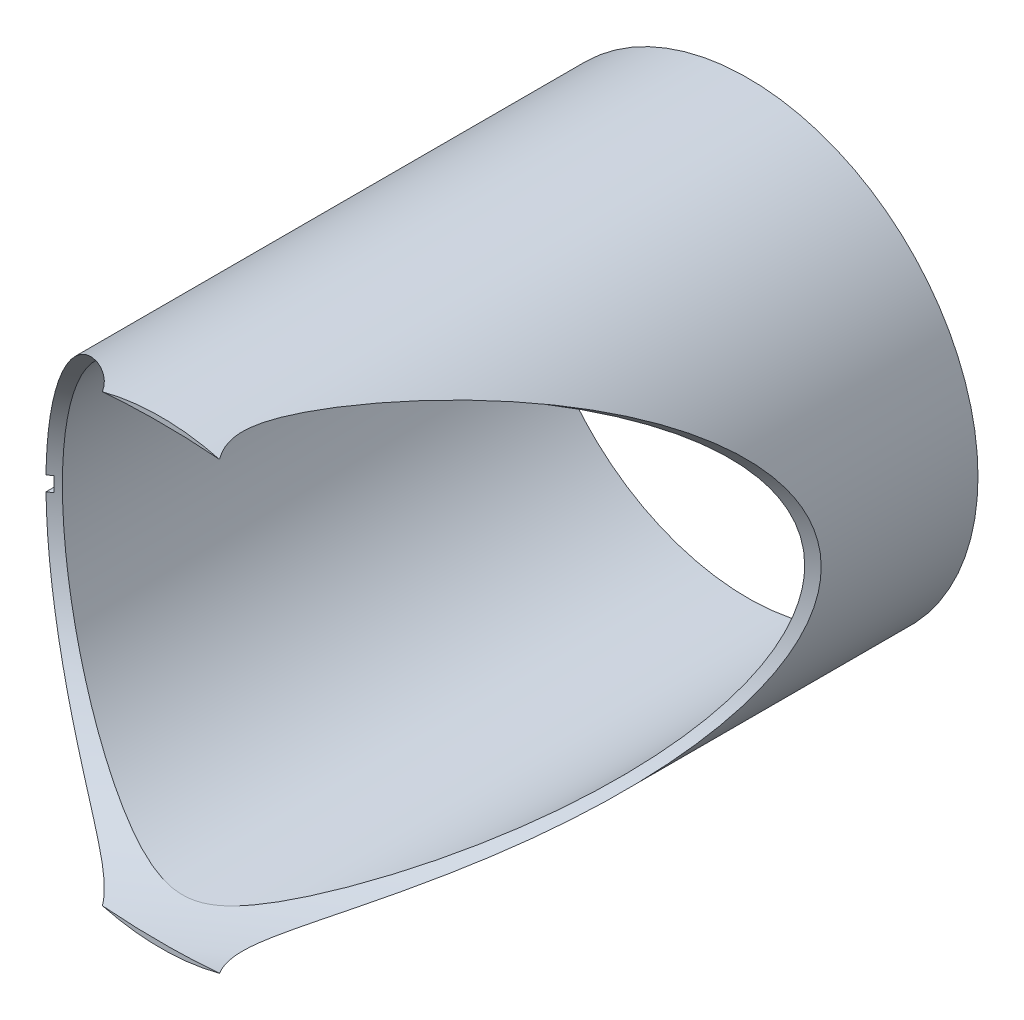
SolidWorks part; units mm, degrees
ref_plane "Front Plane" through (0, 0, 0) normal (0, 0, 1) x (1, 0, 0)
ref_plane "Top Plane" through (0, 0, 0) normal (0, 1, 0) x (1, 0, 0)
ref_plane "Right Plane" through (0, 0, 0) normal (1, 0, 0) x (0, 0, -1)
sketch "Sketch1" plane through (0, 0, 0) normal (0, 0, 1) x (1, 0, 0)
  circle A0 centre (443.1275, 0) radius 22.225 construction
  circle A1 centre (443.1275, 0) radius 22.225 construction
  circle A2 centre (443.1275, 0) radius 23.525
  circle A3 centre (443.1275, 0) radius 22.525
  dimension "D1" = 1.3
  dimension "D2" = 0.3
extrude "Boss-Extrude1" add sketch "Sketch1" against normal blind 60
sketch "Sketch2" plane through (254.325, 0, -174.0591) normal (-0.8252, 0, 0.5648) x (0.5648, 0, 0.8252)
  circle A0 centre (250.2733, 0) radius 23 construction
  circle A1 centre (250.2733, 0) radius 23
extrude "Cut-Extrude1" cut sketch "Sketch2" against normal through all
sketch "Sketch4" plane through (0, 0, -60) normal (0, 0, -1) x (-1, 0, 0)
  line L0 (-420.6025, 0) -> (-419.6025, 0) construction
  line L1 (-420.1025, 0.75) -> (-420.1025, -0.75)
  line L2 (-420.1025, 0.75) -> (-419.6145, 0.75)
  line L3 (-420.1025, -0.75) -> (-419.6145, -0.75)
  circle A0 centre (-443.1275, 0) radius 22.525 construction
  circle A1 centre (-443.1275, 0) radius 23.525 construction
  point P9 (-420.1025, 0)
  dimension "D1" = 1.5
extrude "Cut-Extrude2" cut sketch "Sketch4" against normal through all
